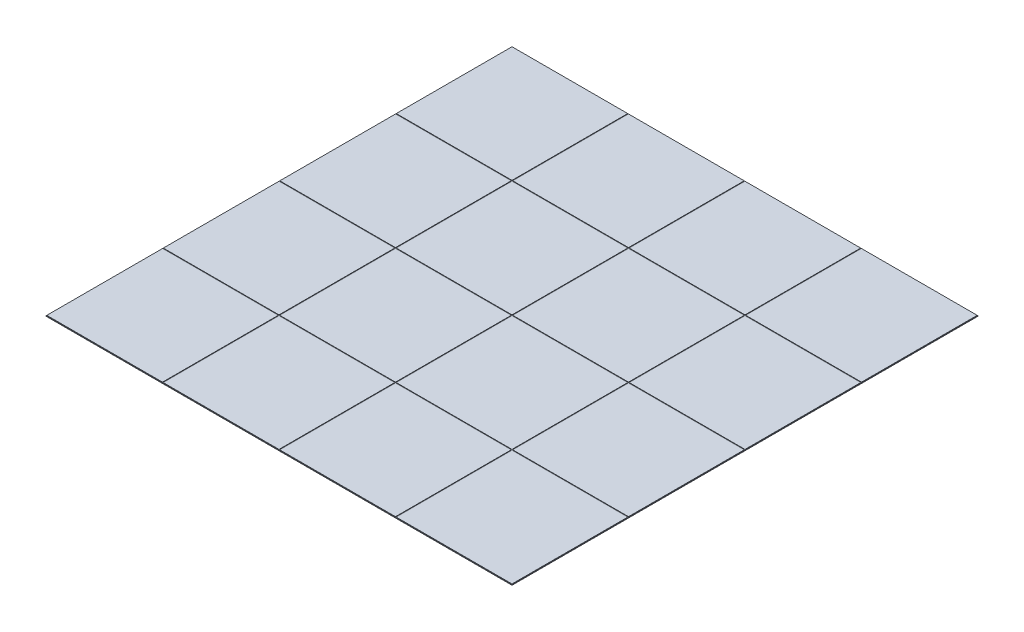
SolidWorks part; units mm, degrees
ref_plane "Front Plane" through (0, 0, 0) normal (0, 0, 1) x (1, 0, 0)
ref_plane "Top Plane" through (0, 0, 0) normal (0, 1, 0) x (1, 0, 0)
ref_plane "Right Plane" through (0, 0, 0) normal (1, 0, 0) x (0, 0, -1)
sketch "Sketch1" plane through (0, 0, 0) normal (0, 1, 0) x (1, 0, 0)
  line L1 (-3000, 3000) -> (3000, 3000)
  line L2 (-3000, 3000) -> (-3000, -3000)
  line L3 (-3000, -3000) -> (3000, -3000)
  line L4 (3000, 3000) -> (3000, -3000)
  line L5 (-3000, 3000) -> (3000, -3000) construction
  line L6 (-3000, -3000) -> (3000, 3000) construction
  point P0 (0, 0)
  dimension "D1" = 6000
  dimension "D2" = 6000
extrude "Boss-Extrude1" add sketch "Sketch1" along normal blind 10
sketch "Sketch2" plane through (0, 10, 0) normal (0, 1, 0) x (1, 0, 0)
  line L0 (-3000, 3000) -> (-1500, 1500) construction
  line L1 (-3000, 3000) -> (3000, 3000)
  line L2 (-3000, 3000) -> (-3000, -3000)
  line L3 (-3000, -3000) -> (3000, -3000)
  line L4 (3000, 3000) -> (3000, -3000)
  line L5 (-3000, 3000) -> (-1500, 3000)
  line L6 (-3000, 3000) -> (-3000, 1500)
  line L7 (-3000, 1500) -> (-1500, 1500)
  line L8 (-1500, 3000) -> (-1500, 1500)
  line L9 (-3000, 1500) -> (-1500, 3000) construction
  line L11 (-2995, 2995) -> (-1505, 2995)
  line L12 (-2995, 2995) -> (-2995, 1505)
  line L13 (-2995, 1505) -> (-1505, 1505)
  line L14 (-1505, 2995) -> (-1505, 1505)
  line L15 (-2995, 2995) -> (-1505, 1505) construction
  line L16 (-2995, 1505) -> (-1505, 2995) construction
  point P9 (-2250, 2250)
  line M3 (-3000, 3000) -> (-3000, -3000)
  dimension "D1" = 1500
  dimension "D2" = 1500
  dimension "D3" = 5
  dimension "D4" = 5
extrude "Cut-Extrude1" cut sketch "Sketch2" against normal blind 5 contours L8 L1 L7 L11 L14 L13 L12 M3 region at (-2250, 10, -2997.8787)
ref_axis "Axis1" through (-3300, 0, 0) along (1, 0, 0)
ref_axis "Axis2" through (0, 0, 3300) along (0, 0, -1)
pattern_linear "LPattern1" count 4 spacing 1500 along (0, 0, 1) count 4 spacing 1500 along (1, 0, 0) of "Cut-Extrude1"
equation "\"FieldSize\"=6000"
equation "\"D1@Sketch1\"=\"FieldSize\""
equation "\"D2@Sketch1\"=\"FieldSize\""
equation "\"CellSize\"=1500"
equation "\"D1@Sketch2\"=\"CellSize\""
equation "\"D2@Sketch2\"=\"CellSize\""
equation "\"GrooveSize\"=5"
equation "\"D3@Sketch2\"=\"GrooveSize\""
equation "\"D4@Sketch2\"=\"GrooveSize\""
equation "\"D1@Cut-Extrude1\"=\"GrooveSize\""
equation "\"D3@LPattern1\"=\"CellSize\""
equation "\"D4@LPattern1\"=\"CellSize\""
